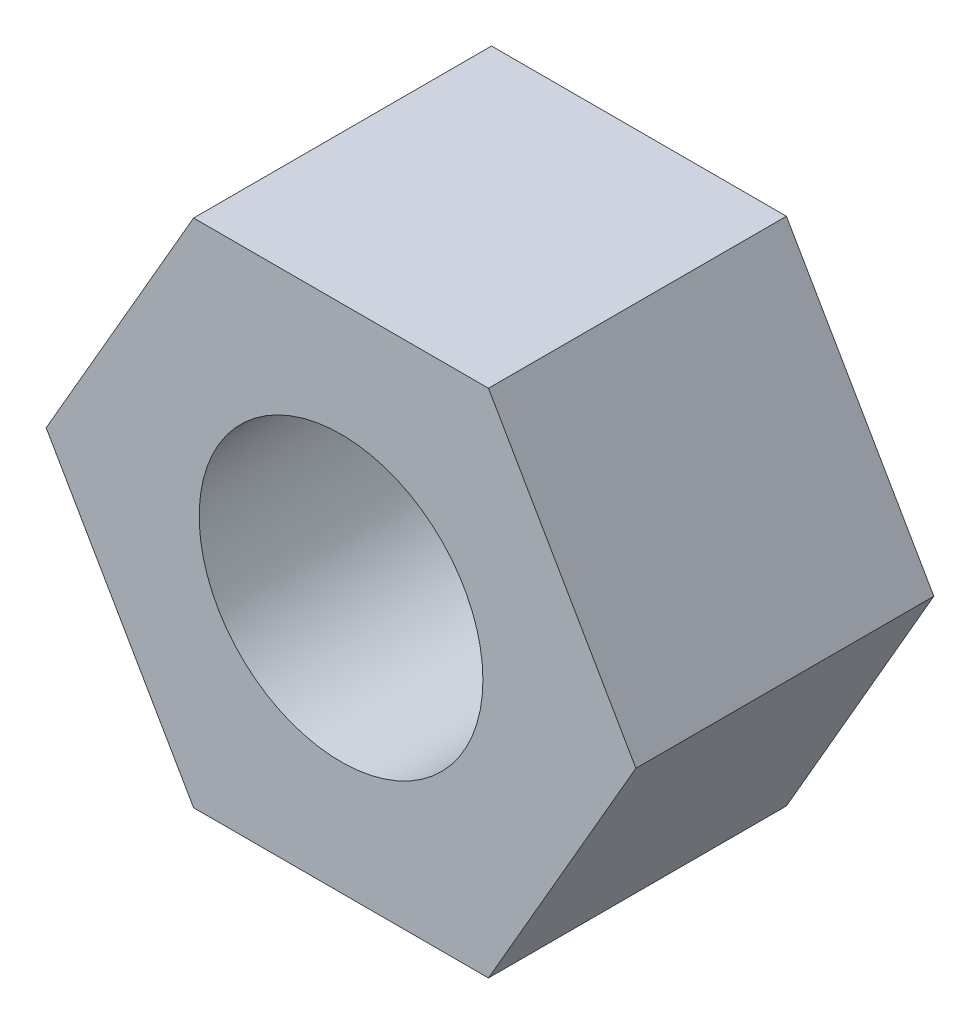
SolidWorks part; units mm, degrees
ref_plane "Front" through (0, 0, 0) normal (0, 0, 1) x (1, 0, 0)
ref_plane "Top" through (0, 0, 0) normal (0, 1, 0) x (1, 0, 0)
ref_plane "Right" through (0, 0, 0) normal (1, 0, 0) x (0, 0, -1)
sketch "Sketch1" plane through (0, 0, 0) normal (0, 0, 1) x (1, 0, 0)
  line L1 (-8.2489, 0) -> (-4.1244, -7.1438)
  line L2 (-4.1244, -7.1438) -> (4.1244, -7.1438)
  line L3 (4.1244, -7.1438) -> (8.2489, 0)
  line L4 (8.2489, 0) -> (4.1244, 7.1438)
  line L5 (4.1244, 7.1438) -> (-4.1244, 7.1438)
  line L6 (-4.1244, 7.1438) -> (-8.2489, 0)
  circle A0 centre (0, 0) radius 7.1438 construction
extrude "Boss-Extrude1" add sketch "Sketch1" along normal blind 8.3344
hole_wizard "3/8-16 Tapped Hole1" positions "Sketch2" profile "Sketch3" tap size "3/8-16" standard "ANSI Inch" end condition through all
sketch "Sketch2" plane through (0, 0, 8.3344) normal (0, 0, 1) x (1, 0, 0)
  point P0 (0, 0)
sketch "Sketch3" plane through (0, 0, 8.3344) normal (1, 0, 0) x (0, -1, 0)
  line L0 (0, 0) -> (0, 8.3344)
  line L1 (0, 8.3344) -> (3.9687, 8.3344)
  line L2 (3.9687, 8.3344) -> (3.9688, 0)
  line L5 (3.9688, 0) -> (0, 0)
  line L11 (0, -6.35) -> (0, 107.95) construction
  dimension "Thru Tap Drill Dia." = 7.9375
  dimension "Thru Tap Drill Depth" = 8.3344
cosmetic thread "Hole Thread1" parameters "D2"=9.525
